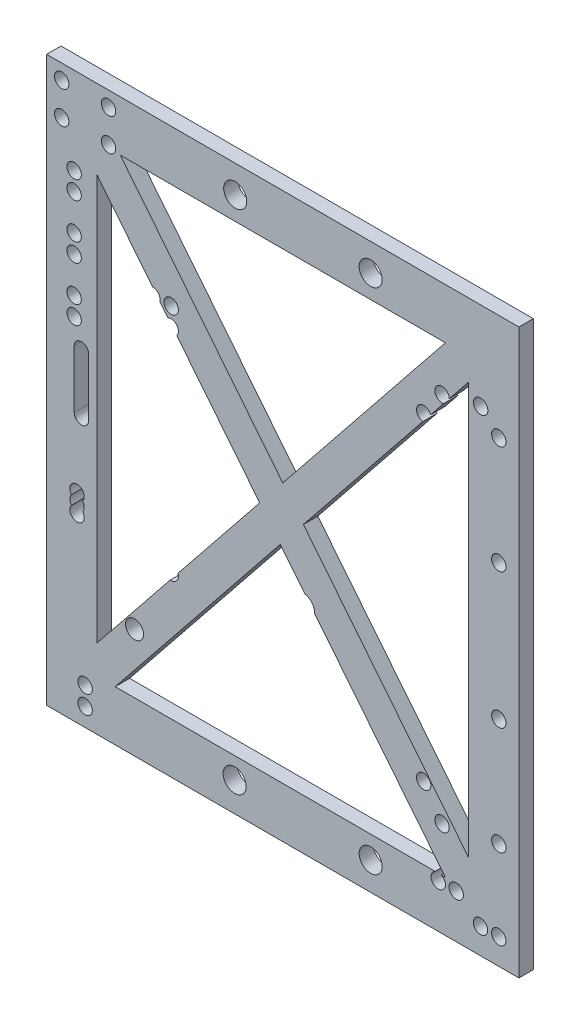
SolidWorks part; units mm, degrees
ref_plane "Front Plane" through (0, 0, 0) normal (0, 0, 1) x (1, 0, 0)
ref_plane "Top Plane" through (0, 0, 0) normal (0, 1, 0) x (1, 0, 0)
ref_plane "Right Plane" through (0, 0, 0) normal (1, 0, 0) x (0, 0, -1)
sketch "Sketch3" plane through (0, 0, 0) normal (0, 0, 1) x (1, 0, 0)
  line L0 (-58.532, 67.237) -> (-58.532, 10.995)
  line L1 (-65.532, 78.232) -> (0, 78.232)
  line L2 (-65.532, 78.232) -> (-65.532, 0)
  line L3 (-65.532, 0) -> (0, 0)
  line L4 (0, 78.232) -> (0, 0)
  line L5 (-56.0191, 7) -> (-10.2051, 7)
  line L6 (-7, 68.0998) -> (-7, 10.995)
  line L8 (-59.706, 45.116) -> (-59.706, 37.116)
  line L9 (-58.532, 71.232) -> (-7, 7) construction
  line L10 (-7, 71.232) -> (-58.532, 7) construction
  line L11 (-55.3269, 71.232) -> (-32.766, 43.111)
  line L12 (-58.532, 67.237) -> (-35.9711, 39.116)
  line L13 (-56.0191, 7) -> (-33.1121, 35.5524)
  line L14 (-58.532, 10.995) -> (-35.9711, 39.116)
  line L15 (-58.532, 71.232) -> (-58.532, 7) construction
  line L16 (-58.532, 7) -> (-7, 7) construction
  line L17 (-33.1121, 35.5524) -> (-10.2051, 7)
  line L18 (-32.766, 43.111) -> (-10.2051, 71.232)
  line L19 (-29.907, 39.5474) -> (-7, 10.995)
  line L20 (-29.907, 39.5474) -> (-7, 68.0998)
  line L21 (-58.532, 71.232) -> (-7, 71.232) construction
  line L22 (-55.3269, 71.232) -> (-10.2051, 71.232)
  line L23 (-7, 71.232) -> (-7, 7) construction
  line L25 (-61.706, 37.116) -> (-61.706, 45.116)
  circle A0 centre (-61.722, 66.169) radius 1
  circle A1 centre (-61.722, 63.629) radius 1
  circle A2 centre (-61.722, 58.669) radius 1
  circle A3 centre (-61.722, 56.129) radius 1
  circle A4 centre (-61.722, 51.169) radius 1
  circle A6 centre (-63.448, 76.164) radius 1
  circle A7 centre (-63.448, 71.664) radius 1
  circle A8 centre (-56.948, 71.664) radius 1
  circle A9 centre (-56.948, 76.164) radius 1
  circle A10 centre (-39.37, 74.422) radius 1.6
  circle A11 centre (-20.574, 74.422) radius 1.6
  circle A12 centre (-5.3091, 66.04) radius 1
  circle A13 centre (-2.794, 63.504) radius 1
  circle A14 centre (-2.794, 48.514) radius 1
  circle A15 centre (-2.794, 29.718) radius 1
  circle A16 centre (-2.794, 14.728) radius 1
  circle A17 centre (-2.799, 3.556) radius 1
  circle A18 centre (-5.339, 3.556) radius 1
  circle A19 centre (-8.7009, 6.096) radius 1
  circle A20 centre (-11.2009, 6.096) radius 1
  circle A21 centre (-20.574, 3.8909) radius 1.6
  circle A22 centre (-39.4509, 4.064) radius 1.6
  circle A23 centre (-60.198, 5.075) radius 1
  circle A24 centre (-60.198, 2.535) radius 1
  circle A25 centre (-61.32, 25.146) radius 1
  circle A26 centre (-61.32, 26.416) radius 1
  circle A27 centre (-61.32, 27.686) radius 1
  arc A28 (-61.706, 37.116) -> (-59.706, 37.116) centre (-60.706, 37.116) ccw
  arc A32 (-59.706, 45.116) -> (-61.706, 45.116) centre (-60.706, 45.116) ccw
  circle A33 centre (-61.722, 48.629) radius 1
  circle A34 centre (-48.255, 56.627) radius 1
  circle A35 centre (-13.213, 17.018) radius 1
  circle A36 centre (-10.668, 13.208) radius 1
  circle A37 centre (-48.26, 24.628) radius 1
  arc A39 (-47.4775, 53.4581) -> (-48.7004, 54.9823) centre (-48.255, 54.087) ccw
  arc A40 (-49.825, 56.3841) -> (-50.8218, 57.6266) centre (-50.795, 56.627) ccw
  circle A41 centre (-13.203, 61.214) radius 1
  circle A42 centre (-10.668, 64.77) radius 1
  circle A43 centre (-29.959, 29.718) radius 1.6
  circle A44 centre (-53.34, 15.24) radius 1.25
  dimension "D2" = 2
  dimension "D3" = 3.2
  dimension "D8" = 2.5
  dimension "D9" = 2
  dimension "D1" = 7
  dimension "D4" = 2.5
  dimension "D5" = 2.5
  dimension "D6" = 2.5
  dimension "D7" = 18.8769
extrude "Boss-Extrude10" add sketch "Sketch3" along normal blind 2 contours L4 L1 L2 L3 A44 A43 L17 L5 A20 L13 A42 L20 L6 L19 A41 A40 L12 A39 L14 A37 L0 A36 A35 A34 A33 A32 L8 A28 L25 A27 A26 A25 region at (-32.422, 39.1083, 0)
sketch3d "3DSketch1"
  line L0 (0, 0, 2) -> (0, 0, 0) construction
  line L2 (-20.574, 0, 0) -> (-20.574, 0, 2)
  line L3 (-65.532, 0, 0) -> (0, 0, 0) construction
  line L4 (-65.532, 0, 2) -> (0, 0, 2) construction
  dimension "D1" = 20.574
ref_plane "Plane1" through (0, 39.116, 0) normal (0, 1, 0) x (1, 0, 0)
sketch "Sketch5" plane through (0, 0, 0) normal (0, -1, 0) x (1, 0, 0)
  line L0 (-20.574, 2) -> (-20.574, 0)
  line L1 (-39.454, 2) -> (-39.454, 0)
  line L2 (-65.532, 2) -> (0, 2) construction
  line L3 (36.0426, 0) -> (-36.0426, 0) construction
  line L4 (-39.454, 1) -> (-20.574, 1) construction
  line L11 (-33.014, 2) -> (-27.014, 2)
  line L12 (-30.014, 2) -> (-30.014, 7) construction
  line L13 (-27.014, 2) -> (-27.014, 4)
  line L14 (-33.014, 2) -> (-33.014, 4)
  line L15 (-27.014, 2) -> (-27.014, 4)
  line L16 (-33.014, 2) -> (-33.014, 4)
  arc A2 (-33.014, 4) -> (-27.014, 4) centre (-30.014, 4) cw
  circle A3 centre (-30.014, 4.5) radius 1.6
  dimension "D1" = 18.88
